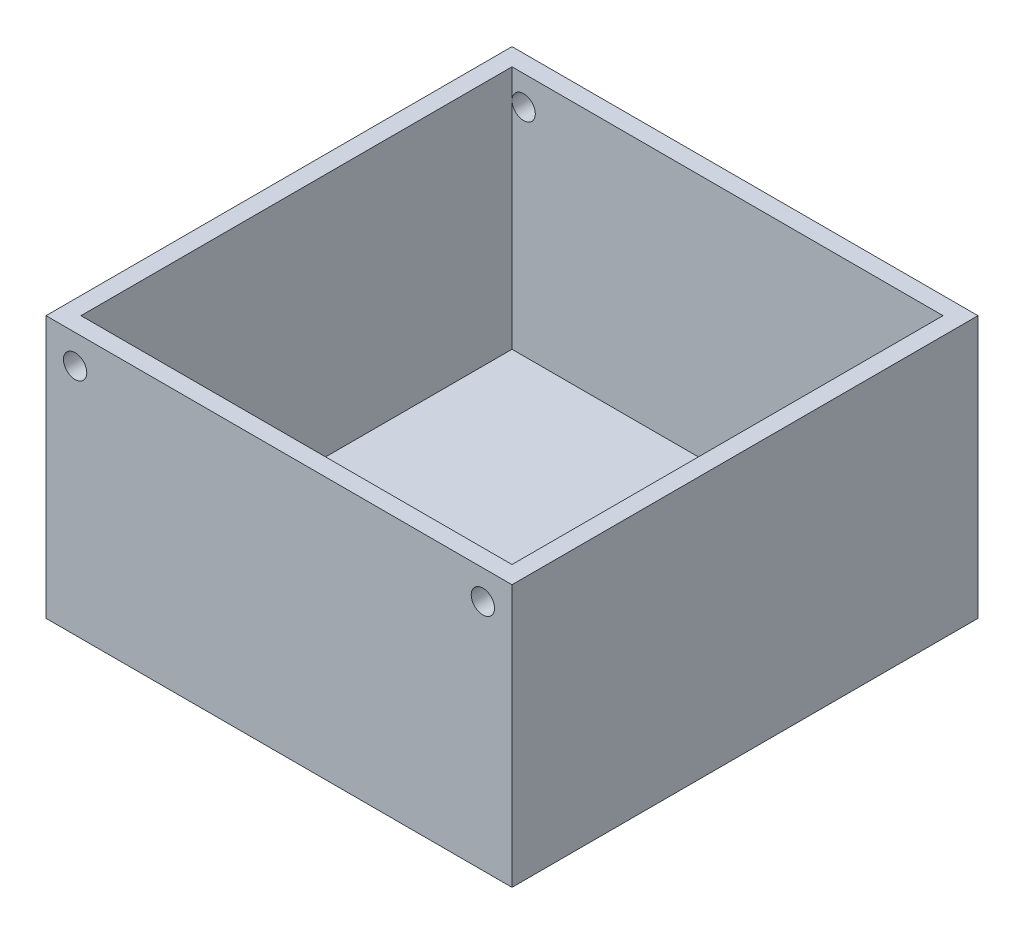
SolidWorks part; units mm, degrees
ref_plane "Front" through (0, 0, 0) normal (0, 0, 1) x (1, 0, 0)
ref_plane "Top" through (0, 0, 0) normal (0, 1, 0) x (1, 0, 0)
ref_plane "Right" through (0, 0, 0) normal (1, 0, 0) x (0, 0, -1)
sketch "Sketch1" plane through (0, 0, 0) normal (0, 0, 1) x (1, 0, 0)
  line L0 (-40, 0) -> (40, 0)
  line L1 (40, 0) -> (40, 45)
  line L2 (-40, 0) -> (-40, 45)
  line L3 (-40, 45) -> (40, 45)
  line L4 (-40, 40) -> (-35, 40) construction
  line L5 (-35, 40) -> (35, 40) construction
  line L6 (35, 40) -> (40, 40) construction
  line L7 (-35, 40) -> (-35, 45) construction
  line L8 (-30, 35) -> (-43, 35)
  line L9 (-43, 35) -> (-43, 55)
  line L10 (-43, 55) -> (-0.1, 55)
  line L11 (-0.1, 55) -> (-0.1, 42.5)
  line L12 (-0.1, 42.5) -> (-30, 42.5)
  line L13 (-30, 42.5) -> (-30, 35)
  line L14 (0, 0) -> (0, 55.7436) construction
  line L15 (-35, 38) -> (-35, 35) construction
  line L16 (30, 35) -> (43, 35)
  line L17 (30, 42.5) -> (30, 35)
  line L18 (0.1, 42.5) -> (30, 42.5)
  line L19 (0.1, 55) -> (0.1, 42.5)
  line L20 (43, 55) -> (0.1, 55)
  line L21 (43, 35) -> (43, 55)
  line L22 (35, 40) -> (35, 42)
  line L23 (35, 42) -> (35, 45)
  line L24 (-35, 36.5) -> (35, 43.5) construction
  line L25 (-35.0995, 37.495) -> (34.9005, 44.495) construction
  line L26 (-34.9005, 35.505) -> (35.0995, 42.505) construction
  circle A0 centre (-35, 40) radius 2
  circle A1 centre (35, 40) radius 2
  arc A2 (-35.0995, 37.495) -> (-34.9005, 35.505) centre (-35, 36.5) ccw construction
  arc A3 (35.0995, 42.505) -> (34.9005, 44.495) centre (35, 43.5) ccw construction
  point P3 (0, 0)
  point P25 (-35, 36.5)
  point P32 (35, 43.5)
  point P33 (0, 40)
  dimension "D5" = 4
  dimension "D11" = 1
  dimension "D1" = 80
  dimension "D2" = 45
  dimension "D3" = 5
  dimension "D4" = 3
  dimension "D6" = 6
  dimension "D7" = 3
  dimension "D8" = 20
  dimension "D9" = 0.1
  dimension "D10" = 0.5
extrude "Boss-Extrude1" add sketch "Sketch1" along normal blind 80 contours L19 L3 L11 L12 L13 L8 L2 L0 L1 L16 L17 L18 | A1 L3 L19 L18 L17 L16 L1 | L13 L12 L11 L3 L2 L8 A0 | A0 | A1 region at (0, 20.4459, 0) region at (-39.5887, 40, 0) region at (36.3742, 41.3742, 0) region at (35, 35.4113, 0) region at (-35, 40, 0)
shell "Shell1" thickness 3 removed face at (0, 45, 40)
extrude "Cut-Extrude3" cut sketch "Sketch1<3>" along normal through all both and the other way through all contours A0 | A1 region at (36.3742, 41.3742, 0) region at (-35, 40, 0)
sketch "Sketch1<3>" plane through (0, 0, 0) normal (0, 0, 1) x (1, 0, 0) same geometry as "Sketch1"
equation "\"D7@Sketch1\"=\"D4@Sketch1\""
